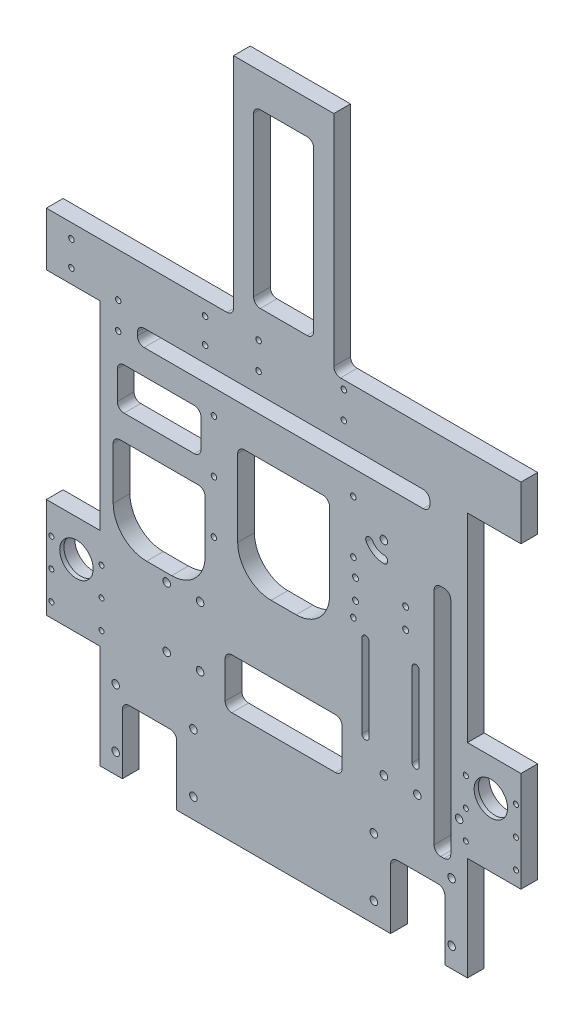
SolidWorks part; units mm, degrees
ref_plane "Front" through (0, 0, 0) normal (0, 0, 1) x (1, 0, 0)
ref_plane "Top" through (0, 0, 0) normal (0, 1, 0) x (1, 0, 0)
ref_plane "Right" through (0, 0, 0) normal (1, 0, 0) x (0, 0, -1)
sketch "Esquisse1" plane through (0, 0, 0) normal (0, 0, 1) x (1, 0, 0)
  line L1 (0, 0) -> (220, 0)
  line L2 (0, 0) -> (0, 285)
  line L3 (0, 285) -> (220, 285)
  line L4 (220, 0) -> (220, 285)
  dimension "D1" = 220
  dimension "D2" = 285
extrude "Boss.-Extru.1" add sketch "Esquisse1" along normal blind 10
sketch "Esquisse2" plane through (0, 0, 0) normal (0, -1, 0) x (1, 0, 0)
  line L0 (0, 5) -> (220, 5) construction
  line L1 (0, 10) -> (0, 0) construction
  line L2 (220, 10) -> (220, 0) construction
  line L3 (110, 5) -> (110, 28.0559) construction
  circle A0 centre (110, 5) radius 2
  circle A1 centre (213, 5) radius 2
  circle A2 centre (7, 5) radius 2
  dimension "D1" = 4
  dimension "D2" = 103
extrude "Enlèv. mat.-Extru.1" cut sketch "Esquisse2" against normal blind 8
sketch "Esquisse3" plane through (0, 0, 10) normal (0, 0, 1) x (1, 0, 0)
  line L0 (110, 0) -> (110, 285) construction
  line L1 (0, 0) -> (220, 0) construction
  line L2 (220, 285) -> (0, 285) construction
  line L3 (82.5, 207) -> (137.5, 207)
  line L4 (137.5, 207) -> (137.5, 137)
  line L5 (137.5, 137) -> (82.5, 137)
  line L6 (82.5, 207) -> (82.5, 137)
  line L8 (8, 175) -> (63, 175)
  line L9 (8, 175) -> (8, 120)
  line L10 (8, 120) -> (63, 120)
  line L11 (63, 175) -> (63, 120)
  line L12 (200, 55) -> (210, 55)
  line L13 (200, 55) -> (200, 195)
  line L14 (200, 195) -> (210, 195)
  line L15 (210, 55) -> (210, 195)
  point P11 (110, 137)
  point P12 (110, 207)
  dimension "D1" = 70
  dimension "D2" = 55
  dimension "D3" = 137
  dimension "D4" = 55
  dimension "D5" = 47
  dimension "D6" = 55
  dimension "D7" = 120
  dimension "D8" = 140
  dimension "D9" = 55
  dimension "D10" = 90
  dimension "D11" = 10
extrude "Enlèv. mat.-Extru.2" cut sketch "Esquisse3" against normal through all both and the other way through all
sketch "Esquisse5" plane through (0, 0, 10) normal (0, 0, 1) x (1, 0, 0)
  line L0 (110, 230) -> (110, 0) construction
  line L1 (22.5, 240) -> (197.5, 240)
  line L2 (22.5, 240) -> (22.5, 230)
  line L3 (22.5, 230) -> (197.5, 230)
  line L4 (197.5, 240) -> (197.5, 230)
  line L5 (0, 0) -> (220, 0) construction
  dimension "D1" = 175
  dimension "D2" = 10
  dimension "D3" = 230
extrude "Enlèv. mat.-Extru.3" cut sketch "Esquisse5" against normal through all both and the other way through all
sketch "Esquisse6" plane through (0, 0, 10) normal (0, 0, 1) x (1, 0, 0)
  line L0 (170, 80) -> (190, 80) construction
  line L1 (0, 0) -> (220, 0) construction
  line L2 (137.5, 137) -> (82.5, 137) construction
  line L3 (215, 80) -> (190, 80) construction
  line L4 (168, 191.6799) -> (168, 168) construction
  line L5 (186.4274, 168) -> (149.5726, 168) construction
  line L6 (0, 285) -> (0, 0) construction
  circle A0 centre (190, 80) radius 2.25
  circle A1 centre (170, 80) radius 2.25
  circle A2 centre (215, 80) radius 2.25
  circle A3 centre (153, 174) radius 1.75
  circle A4 centre (183, 174) radius 1.75
  circle A5 centre (183, 162) radius 1.75
  circle A6 centre (153, 162) radius 1.75
  point P8 (110, 137)
  dimension "D1" = 4.5
  dimension "D3" = 80
  dimension "D6" = 30
  dimension "D7" = 12
  dimension "D8" = 3.5
  dimension "D2" = 20
  dimension "D4" = 60
  dimension "D5" = 25
  dimension "D9" = 168
  dimension "D10" = 168
extrude "Enlèv. mat.-Extru.4" cut sketch "Esquisse6" against normal through all both and the other way through all
sketch "Esquisse7" plane through (0, 0, 10) normal (0, 0, 1) x (1, 0, 0)
  line L0 (110, 0) -> (110, 285) construction
  line L1 (0, 0) -> (220, 0) construction
  line L2 (220, 285) -> (0, 285) construction
  line L3 (68.285, 184) -> (68.285, 215.4) construction
  line L4 (68.285, 184) -> (110, 184) construction
  line L5 (151.715, 184) -> (151.715, 215.4) construction
  line L6 (95, 268) -> (120.5, 268) construction
  line L7 (120.5, 268) -> (120.5, 260) construction
  line L8 (120.5, 260) -> (137.9818, 260) construction
  line L9 (95, 252) -> (120.5, 252) construction
  line L10 (22.5, 240) -> (197.5, 240) construction
  circle A0 centre (68.285, 215.4) radius 1.65
  circle A1 centre (68.285, 184) radius 1.65
  circle A2 centre (68.285, 152.6) radius 1.65
  circle A3 centre (151.715, 152.6) radius 1.65
  circle A4 centre (151.715, 184) radius 1.65
  circle A5 centre (151.715, 215.4) radius 1.65
  circle A6 centre (95, 268) radius 1.65
  circle A7 centre (146, 268) radius 1.65
  circle A8 centre (146, 252) radius 1.65
  circle A9 centre (95, 252) radius 1.65
  dimension "D1" = 31.4
  dimension "D2" = 3.3
  dimension "D5" = 16
  dimension "D6" = 51
  dimension "D9" = 3.3
  dimension "D7" = 15
  dimension "D3" = 83.43
  dimension "D4" = 184
  dimension "D8" = 20
extrude "Enlèv. mat.-Extru.5" cut sketch "Esquisse7" against normal through all both and the other way through all
sketch "Esquisse8" plane through (0, 0, 10) normal (0, 0, 1) x (1, 0, 0)
  line L0 (110, 0) -> (110, 285) construction
  line L1 (0, 0) -> (220, 0) construction
  line L2 (220, 285) -> (0, 285) construction
  line L3 (174, 0) -> (174, 40)
  line L4 (13.5, 0) -> (46, 0)
  line L5 (13.5, 0) -> (13.5, 40)
  line L6 (13.5, 40) -> (46, 40)
  line L7 (46, 0) -> (46, 40)
  line L8 (206.5, 40) -> (174, 40)
  line L9 (206.5, 0) -> (206.5, 40)
  line L10 (206.5, 0) -> (174, 0)
  dimension "D1" = 128
  dimension "D2" = 32.5
  dimension "D3" = 40
extrude "Enlèv. mat.-Extru.6" cut sketch "Esquisse8" against normal through all both and the other way through all
fillet "Congé1" radius 20 4 edges at (137.5, 137, 5) (82.5, 137, 5) (63, 120, 5) (8, 120, 5)
sketch "Esquisse9" plane through (0, 0, 10) normal (0, 0, 1) x (1, 0, 0)
  line L0 (189, 145) -> (189, 95) construction
  line L1 (191.1, 145) -> (191.1, 95)
  line L2 (186.9, 145) -> (186.9, 95)
  line L3 (189, 120) -> (159, 120) construction
  line L4 (174, 120) -> (174, 121.5076) construction
  line L5 (159, 95) -> (159, 145) construction
  line L6 (156.9, 95) -> (156.9, 145)
  line L7 (161.1, 95) -> (161.1, 145)
  line L9 (210, 55) -> (200, 55) construction
  line L10 (200, 55) -> (200, 195) construction
  arc A0 (191.1, 145) -> (186.9, 145) centre (189, 145) ccw
  arc A1 (186.9, 95) -> (191.1, 95) centre (189, 95) ccw
  arc A2 (156.9, 95) -> (161.1, 95) centre (159, 95) ccw
  arc A3 (161.1, 145) -> (156.9, 145) centre (159, 145) ccw
  point P2 (189, 120)
  point P13 (159, 120)
  dimension "D1" = 4.2
  dimension "D2" = 30
  dimension "D3" = 11
  dimension "D4" = 40
  dimension "D5" = 50
extrude "Enlèv. mat.-Extru.7" cut sketch "Esquisse9" against normal through all both and the other way through all
sketch "Esquisse10" plane through (0, 0, 10) normal (0, 0, 1) x (1, 0, 0)
  line L0 (9.5, 0) -> (9.5, 52.9697) construction
  line L1 (0, 0) -> (13.5, 0) construction
  line L2 (0, 285) -> (0, 0) construction
  line L3 (110, 0) -> (110, 48.9194) construction
  line L4 (46, 0) -> (174, 0) construction
  line L5 (32.75, 0) -> (32.75, 52.9697) construction
  circle A0 centre (9.5, 12) radius 2.25
  circle A1 centre (9.5, 47) radius 2.25
  circle A2 centre (210.5, 47) radius 2.25
  circle A3 centre (210.5, 12) radius 2.25
  circle A4 centre (56, 47) radius 2.25
  circle A5 centre (56, 12) radius 2.25
  circle A6 centre (164, 12) radius 2.25
  circle A7 centre (164, 47) radius 2.25
  dimension "D2" = 4.5
  dimension "D3" = 35
  dimension "D4" = 12
  dimension "D5" = 46.5
  dimension "D1" = 9.5
extrude "Enlèv. mat.-Extru.8" cut sketch "Esquisse10" against normal through all both and the other way through all
sketch "Esquisse11" plane through (0, 0, 10) normal (0, 0, 1) x (1, 0, 0)
  line L0 (110, 67) -> (110, 0) construction
  line L1 (75, 97) -> (145, 97)
  line L2 (75, 97) -> (75, 67)
  line L3 (75, 67) -> (145, 67)
  line L4 (145, 97) -> (145, 67)
  line L5 (46, 0) -> (174, 0) construction
  dimension "D1" = 70
  dimension "D2" = 30
  dimension "D3" = 67
extrude "Enlèv. mat.-Extru.9" cut sketch "Esquisse11" against normal through all both and the other way through all
sketch "Esquisse12" plane through (0, 0, 10) normal (0, 0, 1) x (1, 0, 0)
  line L0 (220, 0) -> (220, 285) construction
  line L1 (46, 0) -> (174, 0) construction
  line L2 (170, 202) -> (161.3397, 197) construction
  line L3 (170, 192) -> (170, 202) construction
  circle A0 centre (170, 202) radius 2.25
  arc A1 (161.3397, 197) -> (170, 192) centre (170, 202) ccw construction
  arc A2 (159.3912, 195.875) -> (170, 189.75) centre (170, 202) ccw
  arc A3 (163.2883, 198.125) -> (170, 194.25) centre (170, 202) ccw
  arc A4 (163.2883, 198.125) -> (159.3912, 195.875) centre (161.3397, 197) ccw
  arc A5 (170, 189.75) -> (170, 194.25) centre (170, 192) ccw
  point P9 (165, 193.3397)
  dimension "D1" = 4.5
  dimension "D2" = 50
  dimension "D3" = 202
  dimension "D4" = 4.5
  dimension "D5" = 10
  dimension "D6" = 60
extrude "Enlèv. mat.-Extru.10" cut sketch "Esquisse12" against normal through all both and the other way through all
sketch "Esquisse13" plane through (0, 0, 10) normal (0, 0, 1) x (1, 0, 0)
  line L0 (50, 123.132) -> (50, 97) construction
  line L1 (50, 97) -> (30.3926, 97) construction
  line L2 (46, 0) -> (174, 0) construction
  line L3 (0, 285) -> (0, 0) construction
  circle A0 centre (40, 115) radius 2.25
  circle A1 centre (60, 115) radius 2.25
  circle A2 centre (60, 79) radius 2.25
  circle A3 centre (40, 79) radius 2.25
  dimension "D1" = 36
  dimension "D2" = 20
  dimension "D3" = 4.5
  dimension "D4" = 97
  dimension "D5" = 40
extrude "Enlèv. mat.-Extru.11" cut sketch "Esquisse13" against normal through all both and the other way through all
sketch "Esquisse14" plane through (0, 0, 10) normal (0, 0, 1) x (1, 0, 0)
  line L0 (110, 0) -> (110, 159.9943) construction
  line L1 (0, 285) -> (80, 285)
  line L2 (0, 285) -> (0, 273)
  line L3 (0, 273) -> (80, 273)
  line L4 (80, 285) -> (80, 273)
  line L5 (46, 0) -> (174, 0) construction
  line L6 (140, 285) -> (140, 273)
  line L7 (220, 273) -> (140, 273)
  line L8 (220, 285) -> (220, 273)
  line L9 (220, 285) -> (140, 285)
  dimension "D1" = 12
  dimension "D2" = 80
extrude "Enlèv. mat.-Extru.12" cut sketch "Esquisse14" against normal through all both and the other way through all
sketch "Esquisse15" plane through (0, 0, 10) normal (0, 0, 1) x (1, 0, 0)
  line L0 (140, 285) -> (80, 285) construction
  line L1 (80, 285) -> (140, 285)
  line L2 (80, 285) -> (80, 408)
  line L3 (80, 408) -> (140, 408)
  line L4 (140, 285) -> (140, 408)
  line L5 (110, 408) -> (110, 0) construction
  line L6 (46, 0) -> (174, 0) construction
  dimension "D1" = 60
  dimension "D2" = 123
extrude "Boss.-Extru.2" add sketch "Esquisse15" against normal up to vertex (10 mm away) up to point (13.5, 0, 0)
sketch "Esquisse16" plane through (0, 0, 10) normal (0, 0, 1) x (1, 0, 0)
  line L0 (110, 388) -> (110, 408) construction
  line L1 (92, 285) -> (128, 285)
  line L2 (92, 285) -> (92, 388)
  line L3 (92, 388) -> (128, 388)
  line L4 (128, 285) -> (128, 388)
  line L5 (140, 408) -> (80, 408) construction
  line L6 (140, 273) -> (140, 408) construction
  line L7 (80, 273) -> (0, 273) construction
  dimension "D1" = 12
  dimension "D2" = 20
  dimension "D3" = 12
extrude "Enlèv. mat.-Extru.13" cut sketch "Esquisse16" against normal through all both and the other way through all
sketch "Esquisse17" plane through (0, 0, 10) normal (0, 0, 1) x (1, 0, 0)
  line L0 (110, 0) -> (110, -39.2027) construction
  line L1 (220, 273) -> (252, 273)
  line L2 (220, 273) -> (220, 241)
  line L3 (220, 241) -> (252, 241)
  line L4 (252, 273) -> (252, 241)
  line L5 (46, 0) -> (174, 0) construction
  line L6 (-32, 273) -> (-32, 241)
  line L7 (0, 241) -> (-32, 241)
  line L8 (0, 273) -> (0, 241)
  line L9 (0, 273) -> (-32, 273)
  line L10 (0, 273) -> (0, 0) construction
  line L11 (0, 62) -> (-32, 62)
  line L12 (0, 62) -> (0, 122)
  line L13 (0, 122) -> (-32, 122)
  line L14 (-32, 62) -> (-32, 122)
  line L15 (252, 62) -> (252, 122)
  line L16 (220, 122) -> (252, 122)
  line L17 (220, 62) -> (220, 122)
  line L18 (220, 62) -> (252, 62)
  dimension "D1" = 32
  dimension "D2" = 32
  dimension "D3" = 60
  dimension "D4" = 62
extrude "Boss.-Extru.3" add sketch "Esquisse17" against normal up to vertex (10 mm away) up to point (140, 273, 0)
sketch "Esquisse18" plane through (0, 0, 10) normal (0, 0, 1) x (1, 0, 0)
  line L0 (35.5, 190) -> (35.5, 175) construction
  line L1 (10.5, 190) -> (60.5, 190)
  line L2 (10.5, 190) -> (10.5, 215)
  line L3 (10.5, 215) -> (60.5, 215)
  line L4 (60.5, 190) -> (60.5, 215)
  line L5 (8, 175) -> (63, 175) construction
  dimension "D1" = 25
  dimension "D2" = 50
  dimension "D3" = 15
extrude "Enlèv. mat.-Extru.14" cut sketch "Esquisse18" against normal through all both and the other way through all
fillet "Congé2" radius 4 30 edges at (137.5, 207, 5) (82.5, 207, 5) (197.5, 230, 5) (197.5, 240, 5) (22.5, 240, 5) (22.5, 230, 5) (63, 175, 5) (8, 175, 5) (200, 195, 5) (210, 195, 5) (210, 55, 5) (200, 55, 5) (206.5, 40, 5) (174, 40, 5) (46, 40, 5) (13.5, 40, 5) (75, 67, 5) (145, 67, 5) (145, 97, 5) (75, 97, 5) (92, 388, 5) (128, 388, 5) (128, 285, 5) (92, 285, 5) (140, 273, 5) (80, 273, 5) (10.5, 215, 5) (60.5, 215, 5) (60.5, 190, 5) (10.5, 190, 5)
sketch "Esquisse19" plane through (0, 0, 10) normal (0, 0, 1) x (1, 0, 0)
  line L0 (-32, 257) -> (54.3473, 257) construction
  line L1 (-32, 273) -> (-32, 241) construction
  line L2 (23, 257) -> (23, 269.1) construction
  line L3 (11, 230.8) -> (11, 246.8) construction
  circle A0 centre (-17, 264.5) radius 1.65
  circle A1 centre (-17, 249.5) radius 1.65
  circle A2 centre (63, 249.5) radius 1.65
  circle A3 centre (63, 264.5) radius 1.65
  circle A4 centre (11, 246.8) radius 1.65
  circle A5 centre (11, 230.8) radius 1.65
  dimension "D2" = 80
  dimension "D3" = 3.3
  dimension "D5" = 28
  dimension "D6" = 16
  dimension "D7" = 10.2
  dimension "D1" = 15
  dimension "D4" = 55
extrude "Enlèv. mat.-Extru.15" cut sketch "Esquisse19" against normal through all both and the other way through all
sketch "Esquisse20" plane through (0, 0, 0) normal (0, 0, 1) x (1, 0, 0)
  line L0 (-32, 100) -> (-14, 100) construction
  line L2 (110, 0) -> (110, 74.504) construction
  line L3 (46, 0) -> (174, 0) construction
  line L4 (252, 100) -> (234, 100) construction
  line L5 (-32, 122) -> (-32, 62) construction
  circle A0 centre (-14, 100) radius 11.025
  circle A1 centre (234, 100) radius 11.025
  dimension "D1" = 22.05
  dimension "D3" = 100
  dimension "D2" = 18
extrude "Enlèv. mat.-Extru.16" cut sketch "Esquisse20" along normal blind 7.5
sketch "Esquisse21" plane through (0, 0, 7.5) normal (0, 0, -1) x (-1, 0, 0)
  line L0 (-110, 0) -> (-110, 78) construction
  line L1 (-46, 0) -> (-174, 0) construction
  circle A0 centre (14, 100) radius 10
  circle A1 centre (-234, 100) radius 10
  dimension "D1" = 20
extrude "Enlèv. mat.-Extru.17" cut sketch "Esquisse21" against normal through all both and the other way through all
sketch "Esquisse22" plane through (0, 0, 10) normal (0, 0, 1) x (1, 0, 0)
  line L0 (-14, 104.5) -> (-14, 70.5) construction
  line L1 (-14, 70.5) -> (-29, 70.5) construction
  line L2 (-14, 87.5) -> (-29, 87.5) construction
  line L3 (-14, 104.5) -> (-14, 110) construction
  line L4 (-29, 70.5) -> (-29, 87.5) construction
  line L5 (-14, 110) -> (-4, 100) construction
  line L6 (-24, 100) -> (-14, 110) construction
  line L7 (-24, 100) -> (-4, 100) construction
  line L8 (110, 0) -> (110, 176.4772) construction
  line L9 (46, 0) -> (174, 0) construction
  line L10 (244, 100) -> (224, 100) construction
  line L11 (244, 100) -> (234, 110) construction
  line L12 (234, 110) -> (224, 100) construction
  line L13 (249, 70.5) -> (249, 87.5) construction
  line L14 (234, 104.5) -> (234, 110) construction
  line L15 (234, 87.5) -> (249, 87.5) construction
  line L16 (234, 70.5) -> (249, 70.5) construction
  line L17 (234, 104.5) -> (234, 70.5) construction
  circle A0 centre (-29, 70.5) radius 1.5
  circle A1 centre (-29, 87.5) radius 1.5
  circle A2 centre (-29, 104.5) radius 1.5
  circle A3 centre (1, 104.5) radius 1.5
  circle A4 centre (1, 87.5) radius 1.5
  circle A5 centre (1, 70.5) radius 1.5
  circle A7 centre (-14, 100) radius 10 construction
  circle A8 centre (219, 70.5) radius 1.5
  circle A9 centre (219, 87.5) radius 1.5
  circle A10 centre (219, 104.5) radius 1.5
  circle A11 centre (249, 104.5) radius 1.5
  circle A12 centre (249, 87.5) radius 1.5
  circle A13 centre (249, 70.5) radius 1.5
  dimension "D1" = 3
  dimension "D2" = 30
  dimension "D3" = 17
  dimension "D4" = 12.5
extrude "Enlèv. mat.-Extru.18" cut sketch "Esquisse22" against normal through all both and the other way through all
